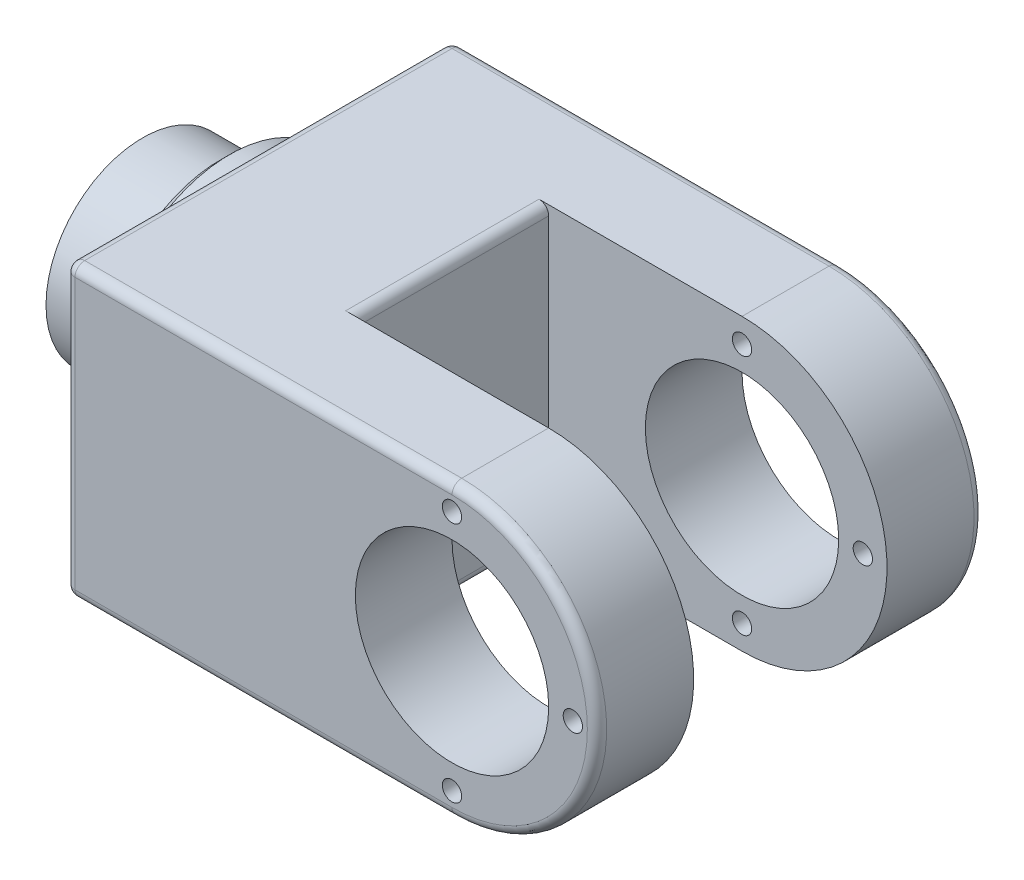
SolidWorks part; units mm, degrees
material "Cast Alloy Steel"
ref_plane "Front Plane" through (0, 0, 0) normal (0, 0, 1) x (1, 0, 0)
ref_plane "Top Plane" through (0, 0, 0) normal (0, 1, 0) x (1, 0, 0)
ref_plane "Right Plane" through (0, 0, 0) normal (1, 0, 0) x (0, 0, -1)
sketch "Sketch1" plane through (0, 0, 0) normal (0, 0, 1) x (1, 0, 0)
  line L1 (0, -75) -> (-200, -75)
  line L3 (0, 75) -> (-200, 75)
  line L4 (-200, -75) -> (-200, 75)
  arc A0 (0, -75) -> (0, 75) centre (0, 0) ccw
  dimension "D1" = 150
  dimension "D2" = 200
  dimension "D3" = 150
extrude "Boss-Extrude1" add sketch "Sketch1" along normal mid plane 200
sketch "Sketch2" plane through (0, 75, 0) normal (0, 1, 0) x (1, 0, 0)
  line L1 (-100, -50) -> (100, -50)
  line L2 (-100, -50) -> (-100, 50)
  line L3 (-100, 50) -> (100, 50)
  line L4 (100, -50) -> (100, 50)
  line L5 (-100, -50) -> (100, 50) construction
  line L6 (-100, 50) -> (100, -50) construction
  point P0 (0, 0)
  dimension "D1" = 100
  dimension "D2" = 200
extrude "Cut-Extrude1" cut sketch "Sketch2" against normal through all
sketch "Sketch3" plane through (-200, 0, 0) normal (-1, 0, 0) x (0, 0, 1)
  circle A0 centre (0, 0) radius 65
  dimension "D1" = 130
extrude "Boss-Extrude2" add sketch "Sketch3" along normal blind 20
sketch "Sketch4" plane through (-220, 0, 0) normal (-1, 0, 0) x (0, 0, 1)
  circle A0 centre (0, 0) radius 50
  dimension "D1" = 100
extrude "Boss-Extrude3" add sketch "Sketch4" along normal blind 40
chamfer "Chamfer1" distance 5 angle 45 1 edges at (-220, 0, 65)
sketch "Sketch5" plane through (0, 0, 100) normal (0, 0, 1) x (1, 0, 0)
  circle A0 centre (0, 0) radius 62.5 construction
  circle A1 centre (0, 62.5) radius 5
  circle A2 centre (0, -62.5) radius 5
  circle A3 centre (62.5, 0) radius 5
  circle A4 centre (0, 0) radius 50
  dimension "D1" = 125
  dimension "D2" = 10
  dimension "D3" = 100
extrude "Cut-Extrude2" cut sketch "Sketch5" against normal through all
fillet "Fillet1" radius 5 14 edges at (-100, -75, 100) (75, 0, 100) (-100, -75, -100) (75, 0, -100) (-220, 0, 50) (-200, 0, 65) (-200, -75, 0) (-200, 0, -100) (-200, 75, 0) (-200, 0, 100) (-100, 75, 100) (-100, 75, -100) (-100, -75, 0) (-100, 75, 0)
